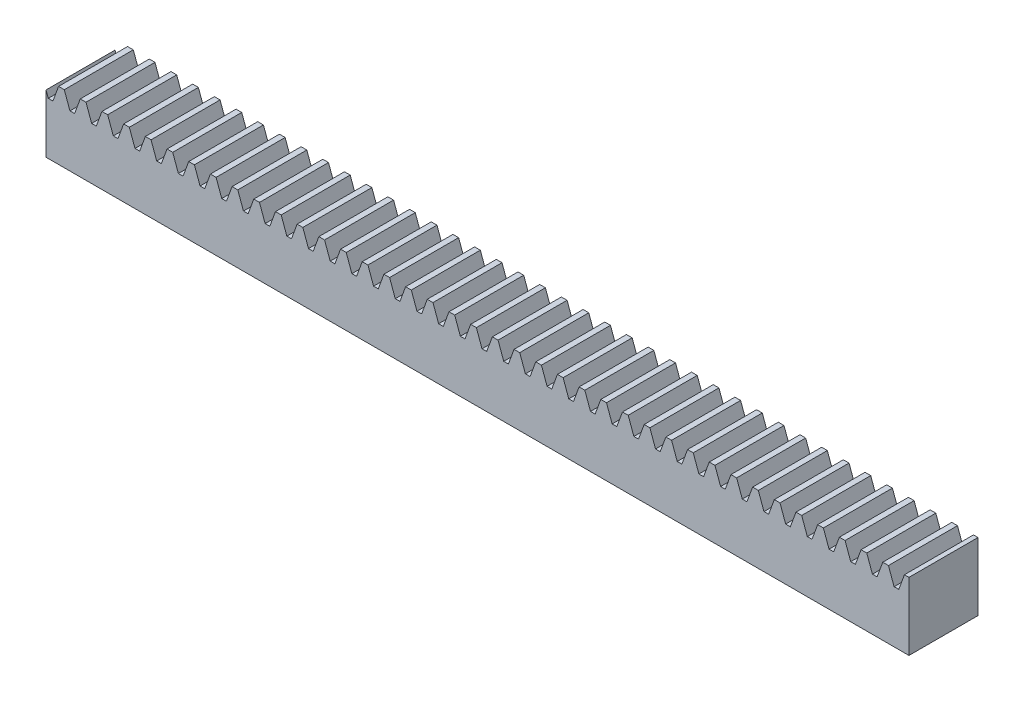
SolidWorks part; units mm, degrees
ref_plane "Front" through (0, 0, 0) normal (0, 0, 1) x (1, 0, 0)
ref_plane "Top" through (0, 0, 0) normal (0, 1, 0) x (1, 0, 0)
ref_plane "Right" through (0, 0, 0) normal (1, 0, 0) x (0, 0, -1)
sketch "Ritning 1" plane through (0, 0, 0) normal (0, 0, 1) x (1, 0, 0)
  line L1 (-124.1, -4.9) -> (125.9, -4.9)
  line L2 (-124.1, -4.9) -> (-124.1, 4.9)
  line L3 (-124.1, 4.9) -> (125.9, 4.9)
  line L4 (125.9, -4.9) -> (125.9, 4.9)
  dimension "D1" = 125.9
  dimension "D2" = 124.1
  dimension "D3" = 4.9
  dimension "D4" = 4.9
extrude "Kuggstångsämne" add sketch "Ritning 1" along normal blind 10
sketch "Ritning 2" plane through (0, 0, 10) normal (0, 0, 1) x (1, 0, 0)
  line L0 (-124.4383, 2.65) -> (-123.7617, 2.65)
  line L1 (-125.2572, 4.9) -> (-124.1, 6.0572)
  line L2 (125.9, -4.9) -> (125.9, 4.9) construction
  line L3 (-124.1, -4.9) -> (125.9, -4.9) construction
  line L7 (-124.1, 6.0572) -> (-122.9428, 4.9)
  line L9 (-122.9428, 4.9) -> (-123.7617, 2.65)
  spline S0 degree 3 poles (-125.2572, 4.9) (-124.9842, 4.15) (-124.7113, 3.4) (-124.4383, 2.65) knots 0 0 0 0 1 1 1 1
  dimension "D1" = 248.8428
  dimension "D2" = 249.6617
  dimension "D3" = 250
  dimension "D4" = 250.3383
  dimension "D5" = 7.55
  dimension "D6" = 9.8
extrude "Kugglucka" cut sketch "Ritning 2" against normal blind 10
ref_axis "Axis" through (125.9, 4.9, 10) along (-1, 0, 0)
pattern_linear "LPattern" count 80 spacing 3.1416 along (1, 0, 0) of "Kugglucka"
sketch "Sketch1" plane through (0, 0, 0) normal (0, 0, -1) x (-1, 0, 0)
  line L0 (-125.9, -4.9) -> (-0.9, -4.9) construction
  line L1 (124.1, -4.9) -> (-125.9, -4.9) construction
  line L2 (-0.9, -4.9) -> (-0.9, 12.5803) construction
  line L4 (-0.9, -4.9) -> (168.5347, -4.9)
  line L5 (-0.9, -4.9) -> (-0.9, 21.191)
  line L6 (-0.9, 21.191) -> (168.5347, 21.191)
  line L7 (168.5347, -4.9) -> (168.5347, 21.191)
  dimension "D1" = 125
extrude "Cut-Extrude1" cut sketch "Sketch1" against normal blind 10
